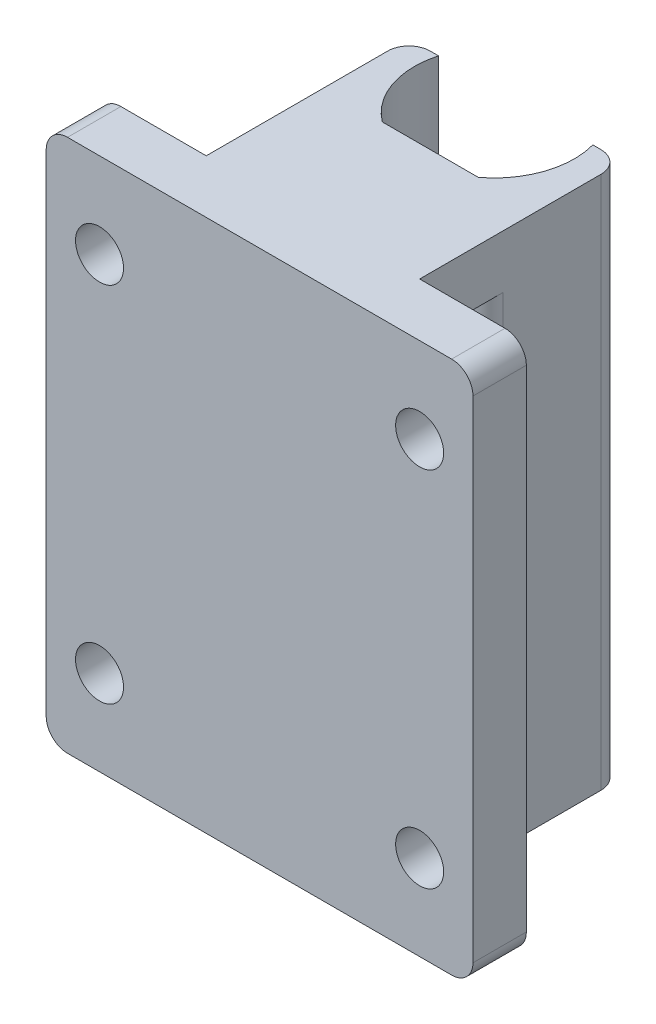
SolidWorks part; units mm, degrees
ref_plane "Front Plane" through (0, 0, 0) normal (0, 0, 1) x (1, 0, 0)
ref_plane "Top Plane" through (0, 0, 0) normal (0, 1, 0) x (1, 0, 0)
ref_plane "Right Plane" through (0, 0, 0) normal (1, 0, 0) x (0, 0, -1)
sketch "Sketch1" plane through (0, 0, 0) normal (0, 1, 0) x (1, 0, 0)
  line L0 (-5.277, 0) -> (34.723, 0)
  line L1 (-5.277, 0) -> (-5.277, 5)
  line L2 (14.723, 0) -> (14.723, 27.5) construction
  line L3 (7.4946, 24) -> (4.723, 24)
  line L4 (4.723, 24) -> (4.723, 5)
  line L5 (4.723, 5) -> (-5.277, 5)
  line L6 (24.723, 5) -> (34.723, 5)
  line L7 (24.723, 24) -> (24.723, 5)
  line L8 (21.9515, 24) -> (24.723, 24)
  line L9 (34.723, 0) -> (34.723, 5)
  arc A0 (21.9515, 24) -> (7.4946, 24) centre (14.723, 22) cw
  point P3 (14.723, 22)
  dimension "D1" = 22
  dimension "D2" = 10
  dimension "D6" = 7.5
  dimension "D3" = 2
  dimension "D4" = 5
  dimension "D5" = 20
extrude "Boss-Extrude1" add sketch "Sketch1" along normal blind 50
ref_plane "Plane1" through (0, 0, -16) normal (0, 0, -1) x (-1, 0, 0)
sketch "Sketch2" plane through (0, 0, -16) normal (0, 0, -1) x (-1, 0, 0)
  line L0 (-7.4946, 50) -> (-7.4946, 0) construction
  line L1 (-21.9515, 50) -> (-7.4946, 50)
  line L2 (-21.9515, 50) -> (-21.9515, 47.5)
  line L3 (-21.9515, 47.5) -> (-7.4946, 47.5)
  line L4 (-7.4946, 50) -> (-7.4946, 47.5)
  line L6 (-21.9515, 0) -> (-7.4946, 0)
  line L7 (-21.9515, 0) -> (-21.9515, 2.5)
  line L8 (-21.9515, 2.5) -> (-7.4946, 2.5)
  line L9 (-7.4946, 0) -> (-7.4946, 2.5)
extrude "Boss-Extrude2" add sketch "Sketch2" against normal blind 10
fillet "Fillet1" radius 2 6 edges at (-5.277, 50, -2.5) (-5.277, 0, -2.5) (34.723, 50, -2.5) (34.723, 0, -2.5) (4.723, 25, -24) (24.723, 25, -24)
sketch "Sketch3" plane through (0, 0, -5) normal (0, 0, -1) x (-1, 0, 0)
  line L0 (-32.723, 50) -> (-24.723, 50) construction
  line L1 (-34.723, 48) -> (-34.723, 2) construction
  circle A0 centre (-29.723, 42) radius 2.25
  circle A1 centre (0.277, 42) radius 2.25
  circle A2 centre (0.277, 8) radius 2.25
  circle A3 centre (-29.723, 8) radius 2.25
  dimension "D1" = 8
  dimension "D2" = 5
  dimension "D3" = 2
  dimension "D4" = 2
extrude "Cut-Extrude1" cut sketch "Sketch3" against normal through all
sketch "Sketch4" plane through (4.723, 0, 0) normal (-1, 0, 0) x (0, 0, 1)
  line L0 (-22, 50) -> (-5, 50) construction
  line L1 (-10.8027, 45) -> (-8.8027, 45)
  line L2 (-10.8027, 45) -> (-10.8027, 40)
  line L3 (-10.8027, 40) -> (-8.8027, 40)
  line L4 (-8.8027, 45) -> (-8.8027, 40)
  line L5 (-10.8027, 10) -> (-8.8027, 10)
  line L6 (-10.8027, 10) -> (-10.8027, 5)
  line L7 (-10.8027, 5) -> (-8.8027, 5)
  line L8 (-8.8027, 10) -> (-8.8027, 5)
  dimension "D1" = 5
  dimension "D2" = 2
extrude "Cut-Extrude2" cut sketch "Sketch4" against normal through all
fillet "Fillet2" radius 2 4 edges at (4.723, 42.5, -10.8027) (4.723, 7.5, -10.8027) (24.723, 7.5, -10.8027) (24.723, 42.5, -10.8027)
